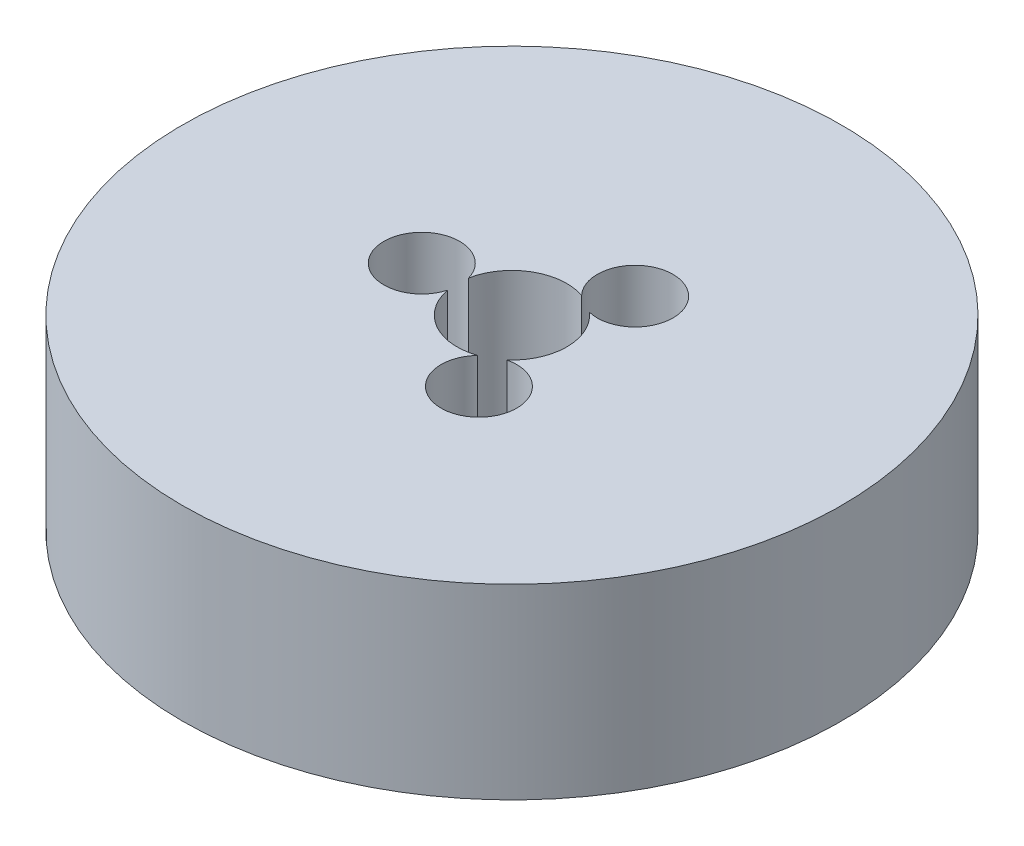
SolidWorks part; units mm, degrees
ref_plane "Front Plane" through (0, 0, 0) normal (0, 0, 1) x (1, 0, 0)
ref_plane "Top Plane" through (0, 0, 0) normal (0, 1, 0) x (1, 0, 0)
ref_plane "Right Plane" through (0, 0, 0) normal (1, 0, 0) x (0, 0, -1)
sketch "Sketch1" plane through (0, 0, 0) normal (0, 1, 0) x (1, 0, 0)
  circle A0 centre (0, 0) radius 30
  dimension "FLANGE_OD" = 60
extrude "Boss-Extrude1" add sketch "Sketch1" along normal blind 17
sketch "Sketch2" plane through (0, 0, 0) normal (0, 1, 0) x (1, 0, 0)
  circle A0 centre (0, 0) radius 5
  dimension "BORE_D" = 10
extrude "Cut-Extrude1" cut sketch "Sketch2" along normal through all
sketch "Sketch3" plane through (0, 17, 0) normal (0, 1, 0) x (1, 0, 0)
  circle A0 centre (0, 0) radius 8.21 construction
  circle A1 centre (-8.21, 0) radius 3.4451
  dimension "BOLT_D" = 6.8902
  dimension "BOLT_PCD" = 16.42
extrude "Cut-Extrude2" cut sketch "Sketch3" against normal blind 12.0421
pattern_circular "CirPattern1" count 3 over 360 about axis through (0, 0, 0) along (0, 1, 0) of "Cut-Extrude2"
